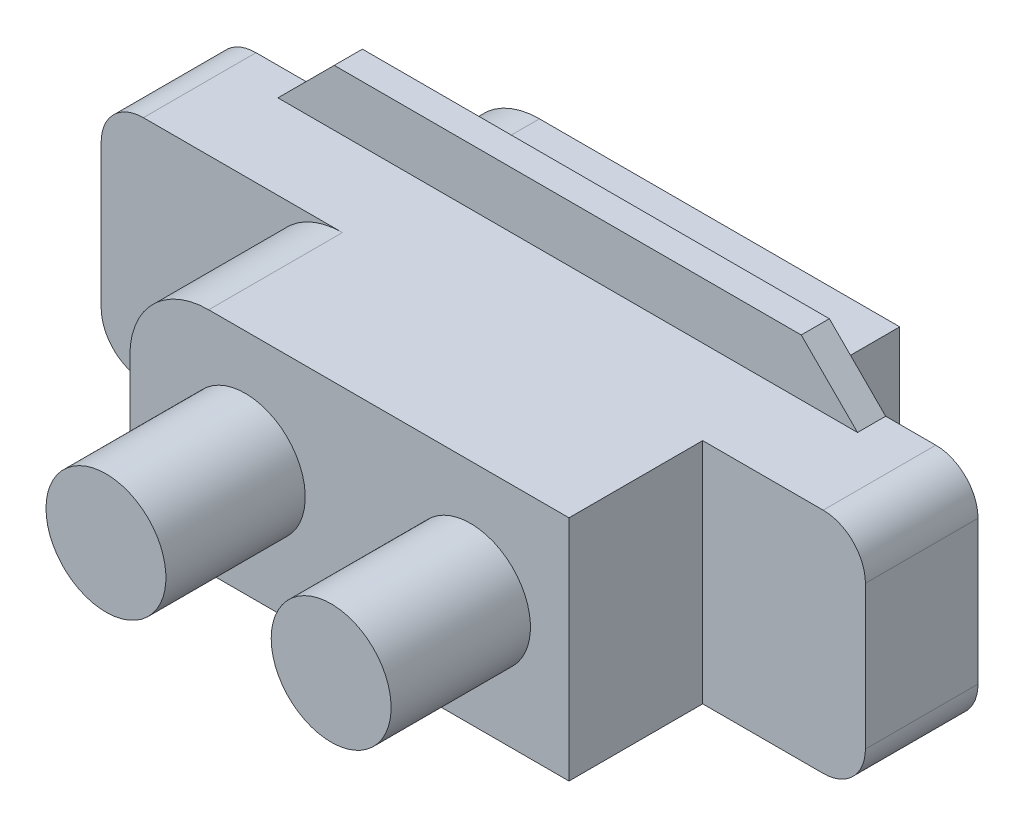
SolidWorks part; units mm, degrees
other "Uwaga1"
sketch "Szkic3" plane through (21.38, 10.1, 0) normal (0.1871, 0.863, -0.4693) x (0.9695, -0.2393, -0.0535)
sketch "Szkic5" plane through (21.38, 10.1, 0) normal (0.1871, 0.863, -0.4693) x (0.9695, -0.2393, -0.0535)
ref_plane "Płaszczyzna przednia" through (0, 0, 0) normal (0, 0, 1) x (1, 0, 0)
ref_plane "Płaszczyzna górna" through (0, 0, 0) normal (0, 1, 0) x (1, 0, 0)
ref_plane "Płaszczyzna prawa" through (0, 0, 0) normal (1, 0, 0) x (0, 0, -1)
sketch "Szkic1" plane through (0, 0, 0) normal (0, 0, 1) x (1, 0, 0)
  line L1 (2.8, 0) -> (15.6, 0)
  line L2 (0, 2.8) -> (0, 5.3)
  line L3 (2.8, 8.1) -> (15.6, 8.1)
  line L4 (15.6, 0) -> (15.6, 8.1)
  arc A0 (2.8, 0) -> (0, 2.8) centre (2.8, 2.8) cw
  arc A1 (0, 5.3) -> (2.8, 8.1) centre (2.8, 5.3) cw
  point P7 (0, 0)
  point P10 (0, 8.1)
  dimension "D3" = 2.8
  dimension "D1" = 8.1
  dimension "D2" = 15.6
extrude "Dodanie-wyciągnięcie1" add sketch "Szkic1" along normal blind 3
sketch "Szkic2" plane through (0, 0, 3) normal (0, 0, 1) x (1, 0, 0)
  line L0 (15.6, 8.1) -> (2.8, 8.1) construction
  line L1 (-0.49, 10.1) -> (16.1, 10.1)
  line L2 (-5.77, 6.6) -> (-5.77, 1.5)
  line L3 (-0.49, -2) -> (16.1, -2)
  line L4 (21.38, 6.6) -> (21.38, 1.5)
  line L5 (0, 5.3) -> (0, 2.8) construction
  line L6 (15.6, 0) -> (15.6, 8.1) construction
  line L8 (16.1, -2) -> (16.1, 0)
  line L9 (2.8, 0) -> (15.6, 0) construction
  line L10 (16.1, 0) -> (19.88, 0)
  line L11 (-0.49, -2) -> (-0.49, 0)
  line L12 (-0.49, 0) -> (-4.27, 0)
  line L13 (-5.77, 4.05) -> (22.4989, 4.05) construction
  line L14 (16.1, 8.1) -> (19.88, 8.1)
  line L15 (16.1, 10.1) -> (16.1, 8.1)
  line L16 (-0.49, 10.1) -> (-0.49, 8.1)
  line L17 (-0.49, 8.1) -> (-4.27, 8.1)
  arc A0 (19.88, 0) -> (21.38, 1.5) centre (19.88, 1.5) ccw
  arc A1 (19.88, 8.1) -> (21.38, 6.6) centre (19.88, 6.6) cw
  arc A2 (-4.27, 8.1) -> (-5.77, 6.6) centre (-4.27, 6.6) ccw
  arc A3 (-4.27, 0) -> (-5.77, 1.5) centre (-4.27, 1.5) cw
  point P25 (21.38, 0)
  point P28 (21.38, 8.1)
  point P31 (-5.77, 8.1)
  point P34 (-5.77, 0)
  dimension "D7" = 1.5
  dimension "D1" = 8.1
  dimension "D2" = 5.77
  dimension "D3" = 2
  dimension "D4" = 5.78
  dimension "D5" = 5.28
  dimension "D6" = 5.28
extrude "Dodanie-wyciągnięcie2" add sketch "Szkic2" along normal blind 1
chamfer "Sfazowanie1" distance 2 angle 45 4 edges at (16.1, 8.1, 3.5) (16.1, 0, 3.5) (-0.49, 0, 3.5) (-0.49, 8.1, 3.5)
sketch "Szkic4" plane through (0, 0, 4) normal (0, 0, 1) x (1, 0, 0)
  line L0 (19.88, 8.1) -> (18.1, 8.1) construction
  line L1 (21.38, 1.5) -> (21.38, 6.6) construction
  line L2 (18.1, 0) -> (19.88, 0) construction
  line L3 (-4.27, 0) -> (-2.49, 0) construction
  line L4 (-5.77, 6.6) -> (-5.77, 1.5) construction
  line L5 (-2.49, 8.1) -> (-4.27, 8.1) construction
  line L6 (19.88, 8.1) -> (18.1, 8.1)
  line L7 (21.38, 1.5) -> (21.38, 6.6)
  line L8 (18.1, 0) -> (19.88, 0)
  line L9 (-4.27, 0) -> (-2.49, 0)
  line L10 (-5.77, 6.6) -> (-5.77, 1.5)
  line L11 (-2.49, 8.1) -> (-4.27, 8.1)
  line L12 (-2.49, 8.1) -> (18.1, 8.1)
  line L13 (18.1, 0) -> (-2.49, 0)
  arc A0 (21.38, 6.6) -> (19.88, 8.1) centre (19.88, 6.6) ccw construction
  arc A1 (19.88, 0) -> (21.38, 1.5) centre (19.88, 1.5) ccw construction
  arc A2 (-5.77, 1.5) -> (-4.27, 0) centre (-4.27, 1.5) ccw construction
  arc A3 (-4.27, 8.1) -> (-5.77, 6.6) centre (-4.27, 6.6) ccw construction
  arc A4 (21.38, 6.6) -> (19.88, 8.1) centre (19.88, 6.6) ccw
  arc A5 (19.88, 0) -> (21.38, 1.5) centre (19.88, 1.5) ccw
  arc A6 (-5.77, 1.5) -> (-4.27, 0) centre (-4.27, 1.5) ccw
  arc A7 (-4.27, 8.1) -> (-5.77, 6.6) centre (-4.27, 6.6) ccw
extrude "Dodanie-wyciągnięcie3" add sketch "Szkic4" along normal blind 3
extrude "Dodanie-wyciągnięcie4" add sketch "Szkic1<2>" along normal blind 4.75 from surface contours A1 L3 L4 L1 A0 L2 starting at face at (7.805, 4.05, 7)
sketch "Szkic1<2>" plane through (0, 0, 0) normal (0, 0, 1) x (1, 0, 0) same geometry as "Szkic1"
sketch "Szkic6" plane through (0, 0, 11.75) normal (0, 0, 1) x (1, 0, 0)
  line L0 (15.6, 0) -> (15.6, 8.1) construction
  circle A0 centre (4.1, 4.05) radius 2.13
  circle A1 centre (12.1, 4.05) radius 2.13
  dimension "D1" = 4.26
  dimension "D2" = 4.26
  dimension "D3" = 8
  dimension "D4" = 3.5
extrude "Dodanie-wyciągnięcie5" add sketch "Szkic6" along normal blind 4.95
